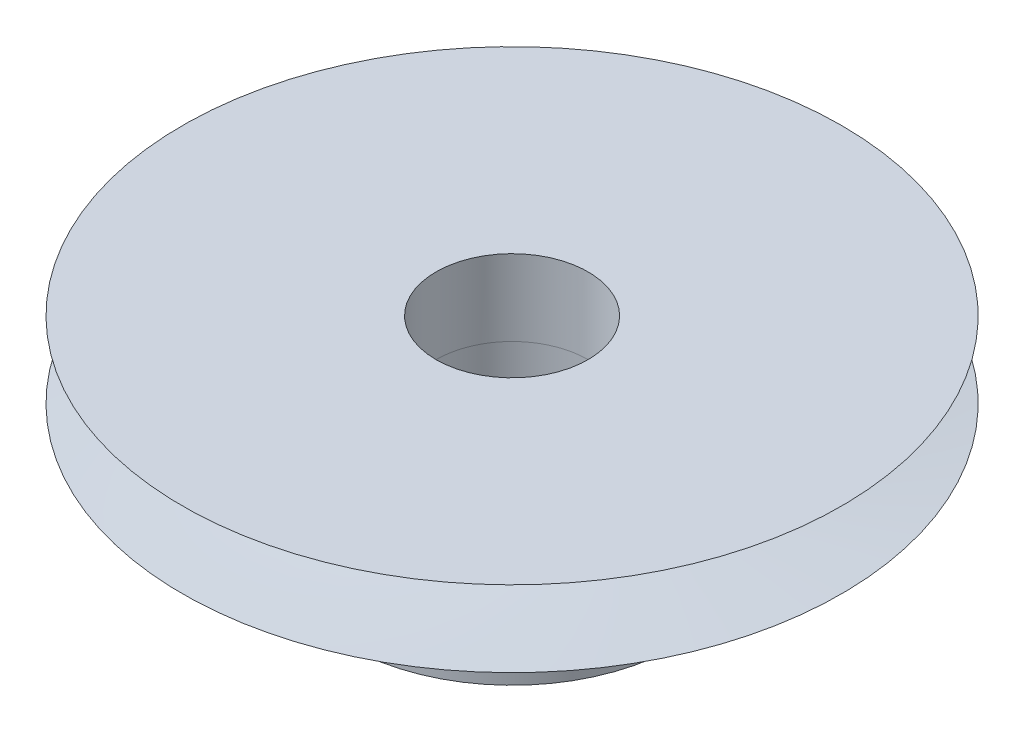
SolidWorks part; units mm, degrees
ref_plane "Front Plane" through (0, 0, 0) normal (0, 0, 1) x (1, 0, 0)
ref_plane "Top Plane" through (0, 0, 0) normal (0, 1, 0) x (1, 0, 0)
ref_plane "Right Plane" through (0, 0, 0) normal (1, 0, 0) x (0, 0, -1)
sketch "Sketch9" plane through (0, 0, 0) normal (0, 0, 1) x (1, 0, 0)
  line L0 (-4.7031, 0.0646) -> (8.2969, -1.4354) construction
  line L1 (-4.7031, -2.9354) -> (8.2969, -2.9354)
  line L3 (-4.7031, 0.0646) -> (8.2969, 0.0646)
  line L4 (8.2969, -2.9354) -> (8.2969, 0.0646)
  line L5 (8.2969, -1.4354) -> (-4.7031, -2.9354) construction
  spline S0 degree 2 poles (-4.7031, 0.0646) (8.2969, -1.4354) (-4.7031, -2.9354) knots 0 0 0 1 1 1
  dimension "D3" = 13
  dimension "D1" = 3
  dimension "D2" = 13
revolve "Revolve1" add sketch "Sketch9" angle 360 about L4
sketch "Sketch117" plane through (0, 0.0646, 0) normal (0, 1, 0) x (1, 0, 0)
  circle A0 centre (8.2969, 0) radius 3
extrude "Cut-Extrude4" cut sketch "Sketch117" against normal blind 3
sketch "Sketch122" plane through (0, -2.9354, 0) normal (0, -1, 0) x (-1, 0, 0)
  circle A0 centre (-8.2969, 0) radius 6.5398
extrude "Boss-Extrude1" add sketch "Sketch122" along normal blind 5
sketch "Sketch123" plane through (0, -2.9354, 0) normal (0, 1, 0) x (1, 0, 0)
  circle A0 centre (8.333, 0) radius 3.036
extrude "Cut-Extrude5" cut sketch "Sketch123" against normal blind 5
hole_wizard "M2x0.4 Tapped Hole1" positions "3DSketch1" profile "Sketch124" tap size "M2x0.4" standard "ANSI Metric" end condition through all
sketch3d "3DSketch1"
  circle A0 centre (8.2969, -2.9354, 0) radius 6.5398 construction
  circle A1 centre (8.2969, -7.9354, 0) radius 6.5398 construction
  point P0 (1.8154, -5.4316, -0.8709)
  point P5 (8.2969, -9.4751, 0)
  point P8 (8.2969, -14.4751, 0)
  dimension "D1" = 7
  dimension "D2" = 7.0027
sketch "Sketch124" plane through (1.8154, -5.4316, -0.8709) normal (0, 1, 0) x (-0.1332, 0, 0.9911)
  line L0 (0, 0) -> (0, 21.1551)
  line L1 (0, 21.1551) -> (0.8, 21.1551)
  line L2 (0.8, 21.1551) -> (0.8, 0)
  line L5 (0.8, 0) -> (0, 0)
  line L11 (0, -6.35) -> (0, 107.95) construction
  dimension "Thru Tap Drill Dia." = 1.6
  dimension "Thru Tap Drill Depth" = 21.1551
cosmetic thread "Hole Thread1" parameters "D2"=2
